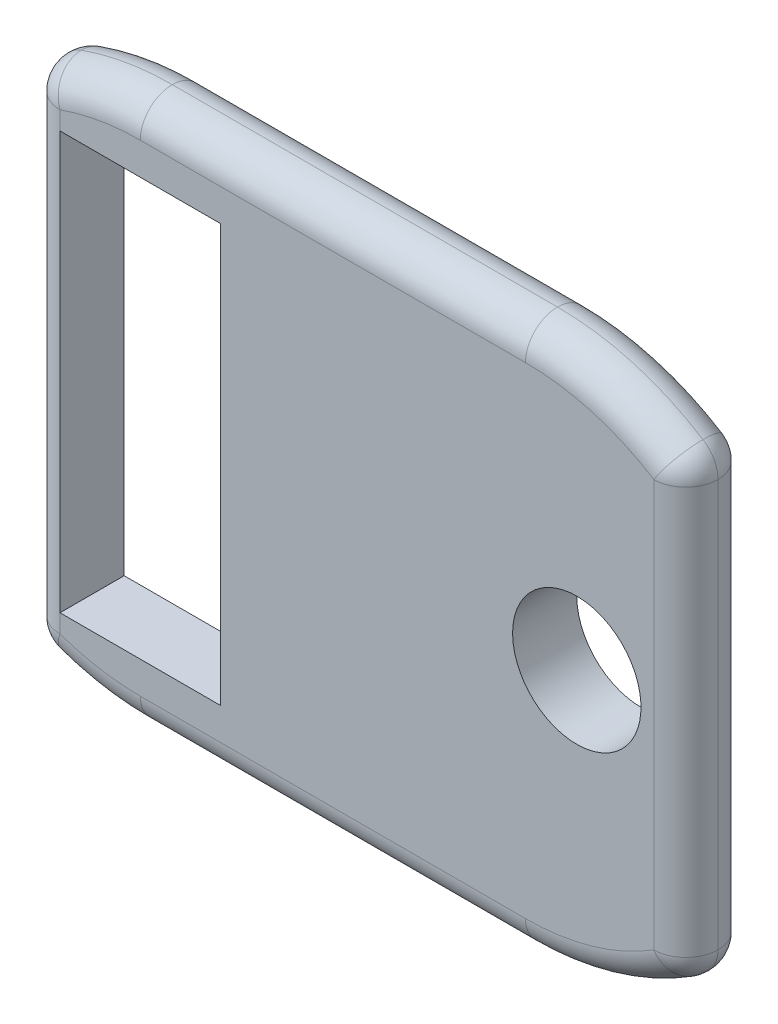
SolidWorks part; units mm, degrees
ref_plane "Front Plane" through (0, 0, 0) normal (0, 0, 1) x (1, 0, 0)
ref_plane "Top Plane" through (0, 0, 0) normal (0, 1, 0) x (1, 0, 0)
ref_plane "Right Plane" through (0, 0, 0) normal (1, 0, 0) x (0, 0, -1)
sketch "Sketch1" plane through (0, 0, 0) normal (0, 0, 1) x (1, 0, 0)
  line L1 (-51.3243, 15.0309) -> (8.6757, 15.0309)
  line L2 (8.6757, 15.0309) -> (8.6757, -69.9691) construction
  line L3 (8.6757, -69.9691) -> (-51.3243, -69.9691)
  line L5 (-68.8243, -66.1989) -> (-68.8243, 11.2608)
  line L6 (33.6757, -61.8384) -> (33.6757, 6.9003)
  arc A0 (-51.3243, 15.0309) -> (-68.8243, 11.2608) centre (-51.3243, -27.4691) ccw
  arc A2 (8.6757, 15.0309) -> (33.6757, 6.9003) centre (8.6757, -27.4691) cw
  arc A3 (-68.8243, -66.1989) -> (-51.3243, -69.9691) centre (-51.3243, -27.4691) ccw
  arc A4 (33.6757, -61.8384) -> (8.6757, -69.9691) centre (8.6757, -27.4691) cw
  dimension "D1" = 60
  dimension "D2" = 25
  dimension "D3" = 17.5
extrude "Boss-Extrude1" add sketch "Sketch1" along normal blind 10
sketch "Sketch2" plane through (0, 0, 0) normal (0, 0, -1) x (-1, 0, 0)
  line L0 (51.3243, 15.0309) -> (51.3243, 5.0309) construction
  line L6 (51.3243, 5.0309) -> (51.3243, -59.9691) construction
  line L8 (38.8243, -59.9691) -> (63.8243, -59.9691)
  line L9 (38.8243, -59.9691) -> (38.8243, 5.0309)
  line L10 (38.8243, 5.0309) -> (63.8243, 5.0309)
  line L11 (63.8243, -59.9691) -> (63.8243, 5.0309)
  line L12 (38.8243, -59.9691) -> (63.8243, 5.0309) construction
  line L13 (38.8243, 5.0309) -> (63.8243, -59.9691) construction
  point P7 (51.3243, -27.4691)
extrude "Cut-Extrude2" cut sketch "Sketch2" against normal blind 20
sketch "Sketch3" plane through (0, 0, 0) normal (0, 0, -1) x (-1, 0, 0)
  line L0 (-33.6757, -61.8384) -> (-33.6757, 6.9003) construction
  circle A0 centre (-16.6757, -27.4691) radius 10
  dimension "D1" = 17
extrude "Cut-Extrude3" cut sketch "Sketch3" against normal blind 20
fillet "Fillet2" radius 5 16 edges at (-60.275, -69.0158, 10) (-60.275, -69.0158, 0) (-21.3243, -69.9691, 10) (-21.3243, -69.9691, 0) (21.8202, -67.8853, 10) (21.8202, -67.8853, 0) (33.6757, -27.4691, 10) (33.6757, -27.4691, 0) (21.8202, 12.9472, 10) (21.8202, 12.9472, 0) (-68.8243, -27.4691, 10) (-68.8243, -27.4691, 0) (-21.3243, 15.0309, 10) (-21.3243, 15.0309, 0) (-60.275, 14.0777, 10) (-60.275, 14.0777, 0)
